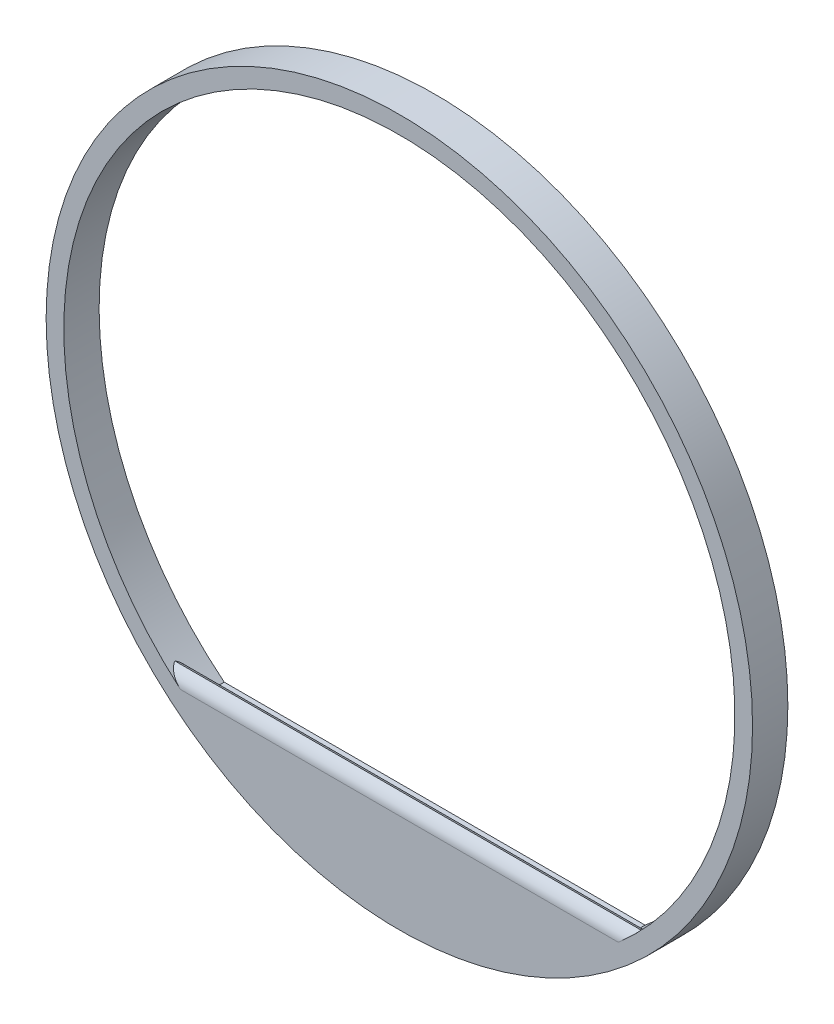
SolidWorks part; units mm, degrees
ref_plane "Plan de face" through (0, 0, 0) normal (0, 0, 1) x (1, 0, 0)
ref_plane "Plan de dessus" through (0, 0, 0) normal (0, 1, 0) x (1, 0, 0)
ref_plane "Plan de droite" through (0, 0, 0) normal (1, 0, 0) x (0, 0, -1)
sketch "Esquisse1" plane through (0, 0, 0) normal (0, 0, 1) x (1, 0, 0)
  circle A0 centre (0, 0) radius 50
  circle A1 centre (0, 0) radius 47.5
  point P1 (-36.2875, -30.6508)
  point P4 (-40.7308, -30.3289)
  dimension "D1" = 100
  dimension "D3" = 95
extrude "Boss.-Extru.1" add sketch "Esquisse1" along normal blind 5 contours A1 A0 region at (-48.5858, 0, 0)
sketch "Esquisse2" plane through (0, 0, 5) normal (0, 0, 1) x (1, 0, 0)
  line L3 (-33.17, -34) -> (33.17, -34)
  arc A6 (33.17, -34) -> (-33.17, -34) centre (0, 0) cw
  dimension "D1" = 34
extrude "Boss.-Extru.2" add sketch "Esquisse2" against normal blind 2.5
fillet "Congé2" radius 2 2 edges at (0, -34, 5) (0, -34, 2.5)
sketch "Esquisse3" plane through (0, 0, 2.5) normal (0, 0, -1) x (-1, 0, 0)
  line L0 (-29.7867, -37) -> (29.7867, -37)
  arc A0 (-30.9879, -36) -> (30.9879, -36) centre (0, 0) ccw construction
  arc A1 (-29.7867, -37) -> (29.7867, -37) centre (0, 0) ccw
  dimension "D1" = 37
extrude "Boss.-Extru.3" add sketch "Esquisse3" along normal blind 2.5
